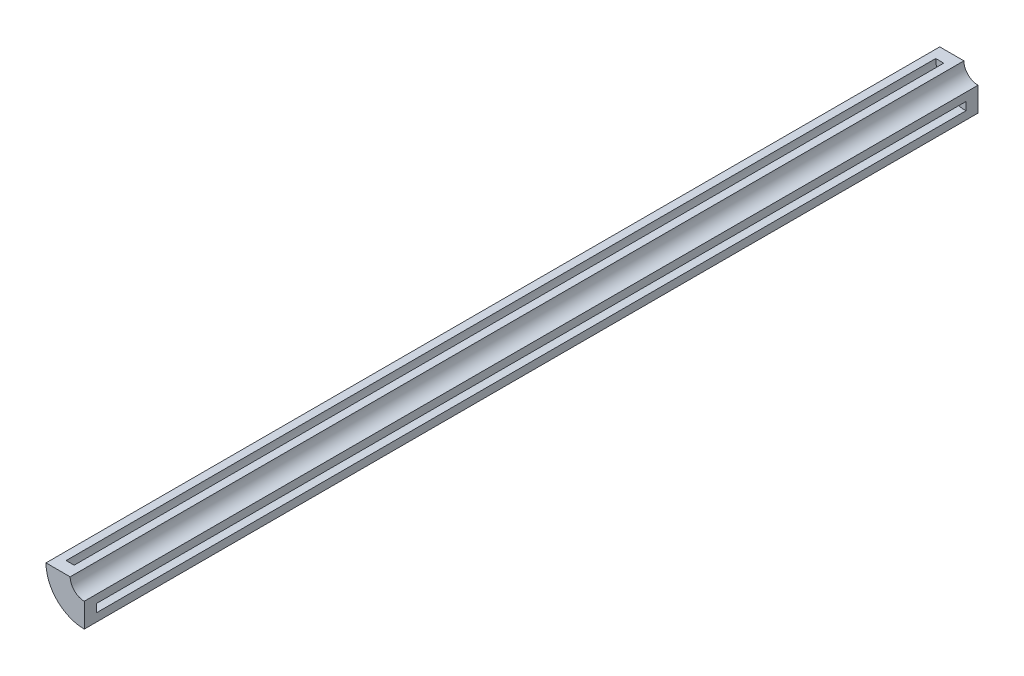
SolidWorks part; units mm, degrees
ref_plane "Front Plane" through (0, 0, 0) normal (0, 0, 1) x (1, 0, 0)
ref_plane "Top Plane" through (0, 0, 0) normal (0, 1, 0) x (1, 0, 0)
ref_plane "Right Plane" through (0, 0, 0) normal (1, 0, 0) x (0, 0, -1)
sketch "Sketch1" plane through (0, 0, 0) normal (0, 0, 1) x (1, 0, 0)
  line L1 (0, -3.5) -> (0, -5.5)
  line L4 (-3.5, 0) -> (-5.5, 0)
  line L5 (-7.5, 0) -> (-9.5, 0)
  line L6 (0, -7.5) -> (0, -9.5)
  arc A0 (-7.5, 0) -> (0, -7.5) centre (0, 0) ccw
  arc A1 (-5.5, 0) -> (0, -5.5) centre (0, 0) ccw
  arc A2 (-9.5, 0) -> (0, -9.5) centre (0, 0) ccw
  arc A3 (-3.5, 0) -> (0, -3.5) centre (0, 0) ccw
  dimension "D1" = 15
  dimension "D2" = 11
  dimension "D3" = 2
extrude "Boss-Extrude1" add sketch "Sketch1" along normal blind 215.9
sketch "Sketch2" plane through (0, 0, 215.9) normal (0, 0, 1) x (1, 0, 0)
  line L0 (-3.5, 0) -> (-9.5, 0)
  line L1 (0, -3.5) -> (0, -9.5)
  arc A0 (-9.5, 0) -> (0, -9.5) centre (0, 0) ccw
  arc A1 (-3.5, 0) -> (0, -3.5) centre (0, 0) ccw
extrude "Boss-Extrude2" add sketch "Sketch2" along normal blind 3
sketch "Sketch3" plane through (0, 0, 0) normal (0, 0, -1) x (-1, 0, 0)
  line L0 (3.5, 0) -> (9.5, 0)
  line L1 (0, -3.5) -> (0, -9.5)
  arc A0 (0, -9.5) -> (9.5, 0) centre (0, 0) ccw
  arc A1 (0, -3.5) -> (3.5, 0) centre (0, 0) ccw
extrude "Boss-Extrude3" add sketch "Sketch3" along normal blind 3
